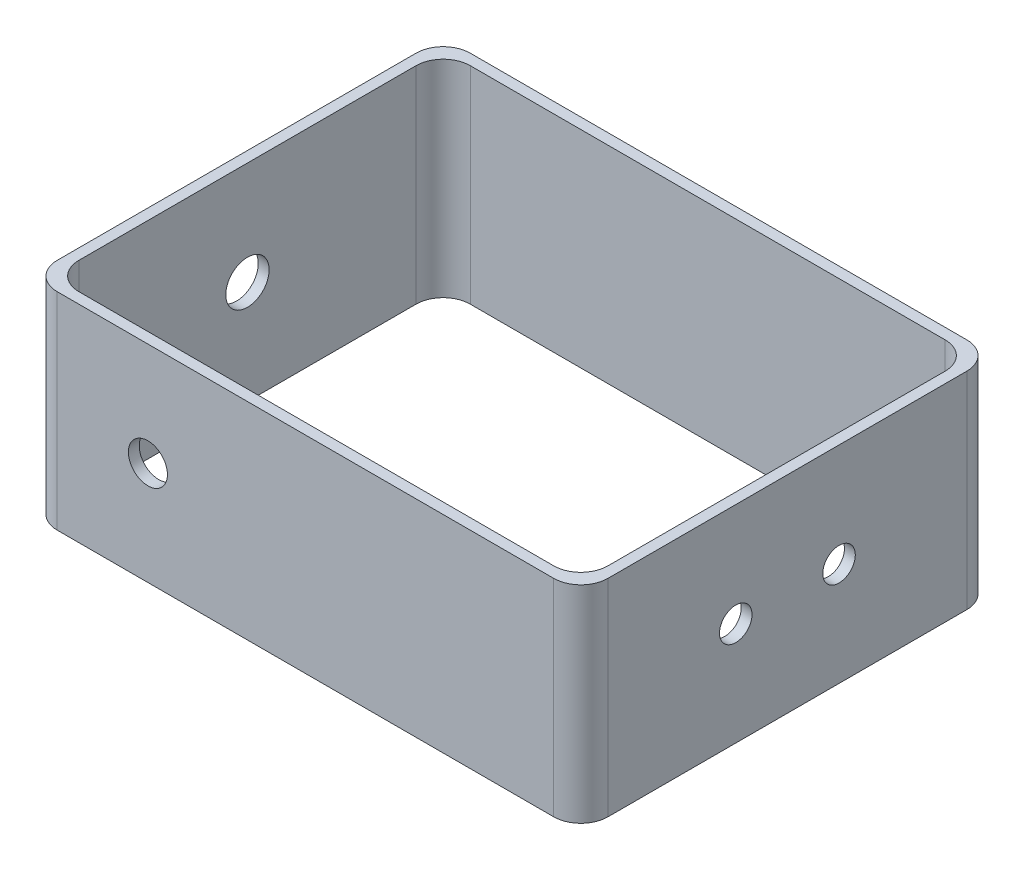
SolidWorks part; units mm, degrees
ref_plane "Front Plane" through (0, 0, 0) normal (0, 0, 1) x (1, 0, 0)
ref_plane "Top Plane" through (0, 0, 0) normal (0, 1, 0) x (1, 0, 0)
ref_plane "Right Plane" through (0, 0, 0) normal (1, 0, 0) x (0, 0, -1)
sketch "Sketch1" plane through (0, 0, 0) normal (0, 1, 0) x (1, 0, 0)
  line L1 (-50.8, 38.1) -> (50.8, 38.1)
  line L2 (-50.8, 38.1) -> (-50.8, -38.1)
  line L3 (-50.8, -38.1) -> (50.8, -38.1)
  line L4 (50.8, 38.1) -> (50.8, -38.1)
  line L5 (-50.8, 38.1) -> (50.8, -38.1) construction
  line L6 (-50.8, -38.1) -> (50.8, 38.1) construction
  point P0 (0, 0)
extrude "Boss-Extrude1" add sketch "Sketch1" along normal blind 38.1
sketch "Sketch3" plane through (0, 38.1, 0) normal (0, 1, 0) x (1, 0, 0)
  line L20 (48.8, -36.1) -> (48.8, 36.1)
  line L21 (-48.8, -36.1) -> (48.8, -36.1)
  line L22 (-48.8, 36.1) -> (-48.8, -36.1)
  line L23 (48.8, 36.1) -> (-48.8, 36.1)
  line L24 (48.8, -36.1) -> (48.8, 36.1)
  line L25 (-48.8, -36.1) -> (48.8, -36.1)
  line L26 (-48.8, 36.1) -> (-48.8, -36.1)
  line L27 (48.8, 36.1) -> (-48.8, 36.1)
  point P0 (0, 0)
  dimension "D1" = 2
extrude "Cut-Extrude1" cut sketch "Sketch3" against normal through all
sketch "Sketch5" plane through (50.8, 0, 0) normal (1, 0, 0) x (0, 0, -1)
  line L0 (0, 0) -> (0, 38.1) construction
  line L1 (-38.1, 0) -> (38.1, 0) construction
  line L2 (-38.1, 38.1) -> (38.1, 38.1) construction
  line L3 (0, 38.1) -> (-38.1, 0) construction
  line L4 (38.1, 0) -> (0, 38.1) construction
  line L5 (0, 0) -> (38.1, 38.1) construction
  line L6 (0, 0) -> (-38.1, 38.1) construction
  point P9 (-19.05, 19.05)
  point P15 (19.05, 19.05)
sketch "Sketch7" plane through (50.8, 0, 0) normal (1, 0, 0) x (0, 0, -1)
  circle A0 centre (-9.525, 19.05) radius 3
  circle A1 centre (9.525, 19.05) radius 3
extrude "Cut-Extrude2" cut sketch "Sketch7" against normal blind 2
sketch "Sketch9" plane through (-50.8, 0, 0) normal (-1, 0, 0) x (0, 0, 1)
  circle A0 centre (0, 19.05) radius 4
extrude "Cut-Extrude3" cut sketch "Sketch9" against normal blind 2
sketch "Sketch10" plane through (0, 0, 38.1) normal (0, 0, 1) x (1, 0, 0)
  line L0 (-50.8, 19.05) -> (50.8, 19.05) construction
  line L1 (-50.8, 38.1) -> (-50.8, 0) construction
  line L2 (50.8, 38.1) -> (50.8, 0) construction
sketch "Sketch11" plane through (0, 0, 38.1) normal (0, 0, 1) x (1, 0, 0)
  line L0 (-50.8, 19.05) -> (50.8, 19.05) construction
  circle A0 centre (-29.0612, 19.05) radius 3.6
extrude "Cut-Extrude4" cut sketch "Sketch11" against normal blind 2
fillet "Fillet1" radius 5 4 edges at (-50.8, 19.05, 38.1) (-50.8, 19.05, -38.1) (50.8, 19.05, -38.1) (50.8, 19.05, 38.1)
fillet "Fillet2" radius 5 4 edges at (48.8, 19.05, -36.1) (48.8, 19.05, 36.1) (-48.8, 19.05, -36.1) (-48.8, 19.05, 36.1)
sketch "Sketch12" [suppressed] plane through (0, 0, 0) normal (0, -1, 0) x (1, 0, 0)
  text T0 "ΔΣ" font "Century Gothic" height in points 60
extrude "Cut-Extrude5" [suppressed] cut sketch "Sketch12" against normal blind 1
